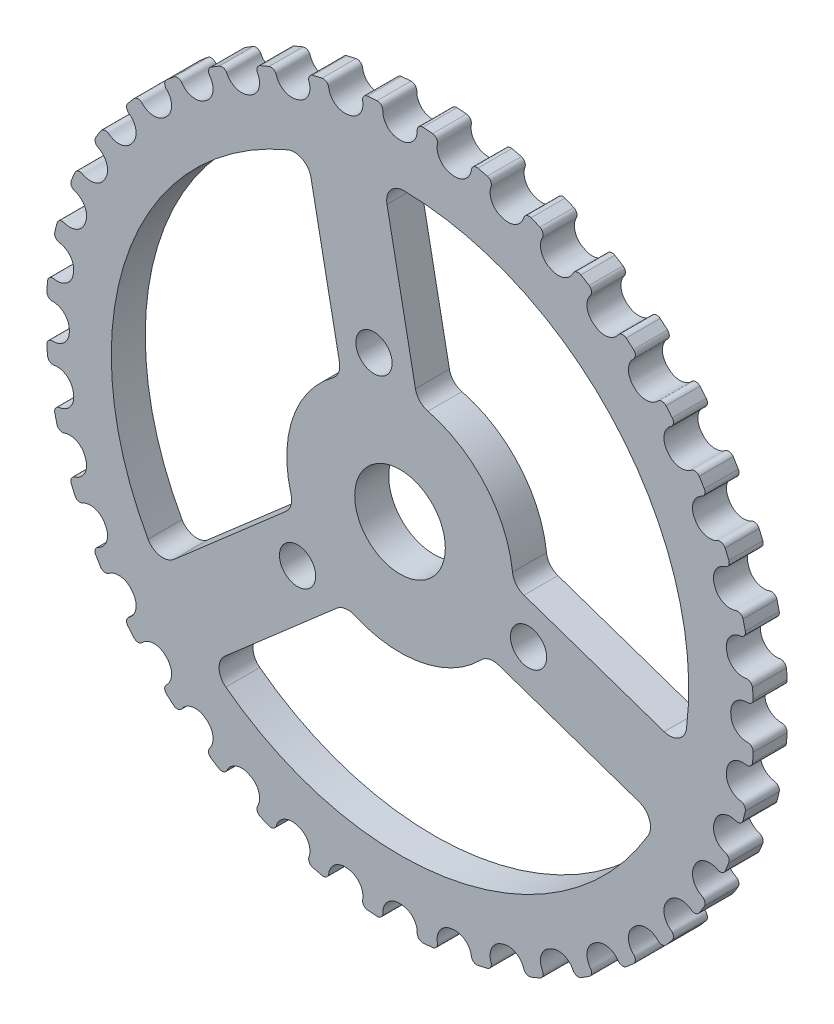
SolidWorks part; units mm, degrees
material "Thornel Mat VMA"
ref_plane "Front Plane" through (0, 0, 0) normal (0, 0, 1) x (1, 0, 0)
ref_plane "Top Plane" through (0, 0, 0) normal (0, 1, 0) x (1, 0, 0)
ref_plane "Right Plane" through (0, 0, 0) normal (1, 0, 0) x (0, 0, -1)
ref_axis "Axis1" through (0, 0, 55) along (0, 0, -1)
sketch "SketchRevolveGearBelt01" plane through (0, 0, 0) normal (1, 0, 0) x (0, 0, -1)
  line L0 (0, 0) -> (1, 0) construction
  line L1 (1.5, 0) -> (1.5, 31.2595)
  line L2 (1.5, 31.2595) -> (-1.5, 31.2595)
  line L3 (-1.5, 31.2595) -> (-1.5, 0)
  line L4 (-1.5, 0) -> (1.5, 0)
  dimension "GearBeltSide1" = 1.5
  dimension "GearBeltOutsideDiameter" = 31.2595
  dimension "GearBeltSide2" = 1.5
revolve "GearBelt01" add sketch "SketchRevolveGearBelt01" angle 360 about L0
sketch "SketchToothGearBelt01" plane through (0, 0, 0) normal (0, 0, 1) x (1, 0, 0)
  arc A0 (31.193, 2.0389) -> (31.193, -2.0389) centre (0, 0) cw
  spline S0 degree 3 poles (31.193, -2.0389) (31.1948, -2.0123) (31.1941, -1.9723) (31.1867, -1.9195) (31.178, -1.8806) (31.1661, -1.8425) (31.1511, -1.8054) (31.1331, -1.7698) (31.1123, -1.7357) (31.0888, -1.7034) (31.0627, -1.6731) (31.0343, -1.6451) (31.0036, -1.6195) (30.971, -1.5965) (30.9365, -1.5763) (30.9006, -1.5589) (30.8633, -1.5445) (30.825, -1.5332) (30.7859, -1.5251) (30.7463, -1.5201) (30.6992, -1.5186) (30.6277, -1.5196) (30.532, -1.516) (30.4198, -1.5026) (30.309, -1.4805) (30.2002, -1.4498) (30.0943, -1.4107) (29.9917, -1.3633) (29.8931, -1.3081) (29.7992, -1.2453) (29.7105, -1.1753) (29.6276, -1.0986) (29.5509, -1.0156) (29.481, -0.9268) (29.4182, -0.8329) (29.363, -0.7343) (29.3157, -0.6317) (29.2767, -0.5257) (29.246, -0.4169) (29.224, -0.3061) (29.2106, -0.1939) (29.2075, -0.1051) (29.2078, -0.0405) (29.2077, 0) (29.2078, 0.0405) (29.2075, 0.1051) (29.2106, 0.1939) (29.224, 0.3061) (29.246, 0.4169) (29.2767, 0.5257) (29.3157, 0.6317) (29.363, 0.7343) (29.4182, 0.8329) (29.481, 0.9268) (29.5509, 1.0156) (29.6276, 1.0986) (29.7105, 1.1753) (29.7992, 1.2453) (29.8931, 1.3081) (29.9917, 1.3633) (30.0943, 1.4107) (30.2002, 1.4498) (30.309, 1.4805) (30.4198, 1.5026) (30.532, 1.516) (30.6277, 1.5196) (30.6992, 1.5186) (30.7463, 1.5201) (30.7859, 1.5251) (30.825, 1.5332) (30.8633, 1.5445) (30.9006, 1.5589) (30.9365, 1.5763) (30.971, 1.5965) (31.0036, 1.6195) (31.0343, 1.6451) (31.0627, 1.6731) (31.0888, 1.7034) (31.1123, 1.7357) (31.1331, 1.7698) (31.1511, 1.8054) (31.1661, 1.8425) (31.178, 1.8806) (31.1867, 1.9195) (31.1941, 1.9723) (31.1948, 2.0123) (31.193, 2.0389) knots 0 0 0 0 0.012476 0.018713 0.024951 0.031189 0.037427 0.043665 0.049903 0.05614 0.062378 0.068616 0.074854 0.081092 0.08733 0.093567 0.099805 0.106043 0.112281 0.118519 0.124756 0.134376 0.152024 0.169672 0.18732 0.204968 0.222616 0.240264 0.257912 0.27556 0.293208 0.310856 0.328503 0.346151 0.363799 0.381447 0.399095 0.416743 0.434391 0.452039 0.469687 0.487335 0.493667 0.5 0.506333 0.512665 0.530313 0.547961 0.565609 0.583257 0.600905 0.618553 0.636201 0.653849 0.671497 0.689144 0.706792 0.72444 0.742088 0.759736 0.777384 0.795032 0.81268 0.830328 0.847976 0.865624 0.875244 0.881481 0.887719 0.893957 0.900195 0.906433 0.91267 0.918908 0.925146 0.931384 0.937622 0.94386 0.950097 0.956335 0.962573 0.968811 0.975049 0.981287 0.987524 1 1 1 1
extrude "ToothExtrudeCutGearBelt01" cut sketch "SketchToothGearBelt01" against normal blind 7.239 and the other way blind 7.239
pattern_circular "PatternGearBelt01" count 40 every 9 about axis through (0, 0, 55) along (0, 0, -1) of "ToothExtrudeCutGearBelt01"
sketch "BoreRevolveSketch" plane through (0, 0, 0) normal (1, 0, 0) x (0, 0, -1)
  line L0 (0, 0) -> (1, 0) construction
  line L1 (-7.239, 0) -> (7.239, 0)
  line L2 (7.239, 0) -> (7.239, 4)
  line L3 (7.239, 4) -> (-7.239, 4)
  line L4 (-7.239, 4) -> (-7.239, 0)
  dimension "BoreSide1" = 7.239
  dimension "TaperSide1" = 4
  dimension "BoreSide2" = 7.239
  dimension "TaperSide2" = 4
revolve "BoreRevolveCut" cut sketch "BoreRevolveSketch" angle 360 about L0
sketch "AuxiliarySketchGearBelt01" plane through (0, 0, 0) normal (0, 0, 1) x (1, 0, 0)
  circle A0 centre (0, 0) radius 31.831 construction
  dimension "PitchDiameter" = 63.6619
sketch "Sketch1" plane through (0, 0, -1.5) normal (0, 0, -1) x (-1, 0, 0)
  line L0 (5.591, -9.4064) -> (15.4656, -18.0084) construction
  line L1 (-8.7214, -6.6088) -> (-21.1083, -10.8595) construction
  line L2 (10.0841, -4.2486) -> (19.9587, -12.8506) construction
  line L3 (5.3507, 9.5451) -> (7.863, 22.3978) construction
  line L4 (-10.9417, -0.1387) -> (-23.3286, -4.3894) construction
  line L5 (-1.3627, 10.8574) -> (1.1496, 23.7101) construction
  line L6 (5.591, -9.4064) -> (15.4656, -18.0084)
  line L7 (-8.7214, -6.6088) -> (-21.1083, -10.8595)
  line L8 (10.0841, -4.2486) -> (19.9587, -12.8506)
  line L9 (5.3507, 9.5451) -> (7.863, 22.3978)
  line L10 (-10.9417, -0.1387) -> (-23.3286, -4.3894)
  line L11 (-1.3627, 10.8574) -> (1.1496, 23.7101)
  arc A0 (-21.9103, -13.0456) -> (15.3854, -20.3357) centre (0, 0) ccw construction
  arc A1 (15.3854, -20.3357) -> (15.4656, -18.0084) centre (14.4804, -19.1395) ccw construction
  arc A2 (-21.1083, -10.8595) -> (-21.9103, -13.0456) centre (-20.6215, -12.2782) ccw construction
  circle A3 centre (9.0483, -7.8822) radius 1.6 construction
  circle A4 centre (2.302, 11.7771) radius 1.6 construction
  circle A5 centre (-11.3503, -3.8949) radius 1.6 construction
  arc A6 (-7.1605, -6.9805) -> (-8.7214, -6.6088) centre (-8.2346, -8.0276) ccw construction
  arc A7 (19.9587, -12.8506) -> (22.253, -12.4521) centre (20.944, -11.7196) ccw construction
  arc A8 (5.591, -9.4064) -> (4.005, -9.163) centre (4.6057, -10.5374) ccw construction
  arc A9 (-7.1605, -6.9805) -> (4.005, -9.163) centre (0, 0) ccw construction
  arc A10 (9.6255, -2.7109) -> (10.0841, -4.2486) centre (11.0694, -3.1175) ccw construction
  arc A11 (9.6255, -2.7109) -> (5.9329, 8.0499) centre (0, 0) ccw construction
  arc A12 (5.3507, 9.5451) -> (5.9329, 8.0499) centre (6.8228, 9.2574) ccw construction
  arc A13 (22.253, -12.4521) -> (9.9185, 23.492) centre (0, 0) ccw construction
  arc A14 (9.9185, 23.492) -> (7.863, 22.3978) centre (9.3351, 22.1101) ccw construction
  arc A15 (-25.3039, -3.1563) -> (-23.3286, -4.3894) centre (-23.8154, -2.9706) ccw construction
  arc A16 (-10.9417, -0.1387) -> (-9.9379, 1.1131) centre (-11.4285, 1.28) ccw construction
  arc A17 (-2.4651, 9.6914) -> (-1.3627, 10.8574) centre (-2.8348, 11.1451) ccw construction
  arc A18 (-2.4651, 9.6914) -> (-9.9379, 1.1131) centre (0, 0) ccw construction
  arc A19 (1.1496, 23.7101) -> (-0.3427, 25.4977) centre (-0.3225, 23.9978) ccw construction
  arc A20 (-0.3427, 25.4977) -> (-25.3039, -3.1563) centre (0, 0) ccw construction
  arc A21 (-21.9103, -13.0456) -> (15.3854, -20.3357) centre (0, 0) ccw
  arc A22 (15.3854, -20.3357) -> (15.4656, -18.0084) centre (14.4804, -19.1395) ccw
  arc A23 (-21.1083, -10.8595) -> (-21.9103, -13.0456) centre (-20.6215, -12.2782) ccw
  circle A24 centre (9.0483, -7.8822) radius 1.6
  circle A25 centre (2.302, 11.7771) radius 1.6
  circle A26 centre (-11.3503, -3.8949) radius 1.6
  arc A27 (-7.1605, -6.9805) -> (-8.7214, -6.6088) centre (-8.2346, -8.0276) ccw
  arc A28 (19.9587, -12.8506) -> (22.253, -12.4521) centre (20.944, -11.7196) ccw
  arc A29 (5.591, -9.4064) -> (4.005, -9.163) centre (4.6057, -10.5374) ccw
  arc A30 (-7.1605, -6.9805) -> (4.005, -9.163) centre (0, 0) ccw
  arc A31 (9.6255, -2.7109) -> (10.0841, -4.2486) centre (11.0694, -3.1175) ccw
  arc A32 (9.6255, -2.7109) -> (5.9329, 8.0499) centre (0, 0) ccw
  arc A33 (5.3507, 9.5451) -> (5.9329, 8.0499) centre (6.8228, 9.2574) ccw
  arc A34 (22.253, -12.4521) -> (9.9185, 23.492) centre (0, 0) ccw
  arc A35 (9.9185, 23.492) -> (7.863, 22.3978) centre (9.3351, 22.1101) ccw
  arc A36 (-25.3039, -3.1563) -> (-23.3286, -4.3894) centre (-23.8154, -2.9706) ccw
  arc A37 (-10.9417, -0.1387) -> (-9.9379, 1.1131) centre (-11.4285, 1.28) ccw
  arc A38 (-2.4651, 9.6914) -> (-1.3627, 10.8574) centre (-2.8348, 11.1451) ccw
  arc A39 (-2.4651, 9.6914) -> (-9.9379, 1.1131) centre (0, 0) ccw
  arc A40 (1.1496, 23.7101) -> (-0.3427, 25.4977) centre (-0.3225, 23.9978) ccw
  arc A41 (-0.3427, 25.4977) -> (-25.3039, -3.1563) centre (0, 0) ccw
extrude "Cut-Extrude1" cut sketch "Sketch1" against normal blind 10
